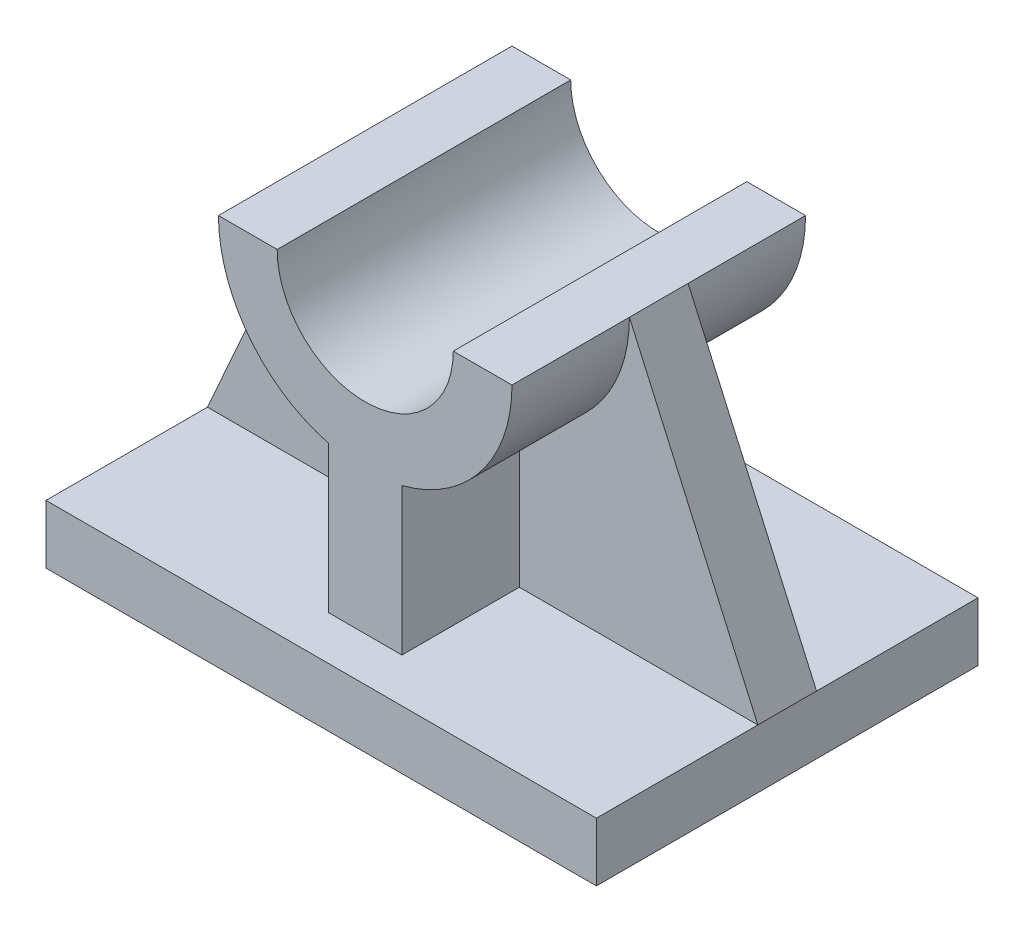
SolidWorks part; units mm, degrees
ref_plane "Front Plane" through (0, 0, 0) normal (0, 0, 1) x (1, 0, 0)
ref_plane "Top Plane" through (0, 0, 0) normal (0, 1, 0) x (1, 0, 0)
ref_plane "Right Plane" through (0, 0, 0) normal (1, 0, 0) x (0, 0, -1)
sketch "Sketch2" plane through (0, 0, 0) normal (0, 0, 1) x (1, 0, 0)
  line L0 (-5, 4) -> (-5, 24)
  line L1 (37.5, -4) -> (-37.5, -4)
  line L2 (37.5, -4) -> (37.5, 4)
  line L3 (37.5, 4) -> (5, 4)
  line L4 (-37.5, -4) -> (-37.5, 4)
  line L5 (37.5, -4) -> (-37.5, 4) construction
  line L6 (37.5, 4) -> (-37.5, -4) construction
  line L7 (5, 4) -> (5, 24)
  line L8 (0, 0) -> (0, 43.3649) construction
  line L9 (12, 43.3649) -> (20, 43.3649)
  line L10 (-12, 43.3649) -> (-20, 43.3649)
  line L11 (-5, 4) -> (-37.5, 4)
  line L12 (-20, 43.3649) -> (-37.5, 4)
  line L13 (20, 43.3649) -> (37.5, 4)
  line L14 (-5, 4) -> (5, 4)
  arc A0 (-20, 43.3649) -> (-5, 24) centre (0, 43.3649) ccw
  arc A1 (-12, 43.3649) -> (12, 43.3649) centre (0, 43.3649) ccw
  arc A2 (5, 24) -> (20, 43.3649) centre (0, 43.3649) ccw
  point P0 (0, 0)
  dimension "D7" = 40
  dimension "D8" = 24
  dimension "D1" = 8
  dimension "D2" = 75
  dimension "D3" = 5
  dimension "D4" = 5
  dimension "D5" = 20
  dimension "D6" = 20
extrude "Boss-Extrude1" add sketch "Sketch2" along normal mid plane 52 contours L14 L11 L4 L1 L2 L3 region at (0, 0, 0)
extrude "Boss-Extrude3" add sketch "Sketch2<4>" along normal mid plane 40 contours L7 A2 L9 A1 L10 A0 L0 L14 region at (0, 26.6876, 0)
sketch "Sketch2<4>" plane through (0, 0, 0) normal (0, 0, 1) x (1, 0, 0) same geometry as "Sketch2"
extrude "Boss-Extrude4" add sketch "Sketch2<6>" along normal mid plane 8 contours A2 L7 L3 L13 | A0 L12 L11 L0 region at (-19.2557, 17.0017, 0) region at (19.2557, 17.0017, 0)
sketch "Sketch2<6>" plane through (0, 0, 0) normal (0, 0, 1) x (1, 0, 0) same geometry as "Sketch2"
